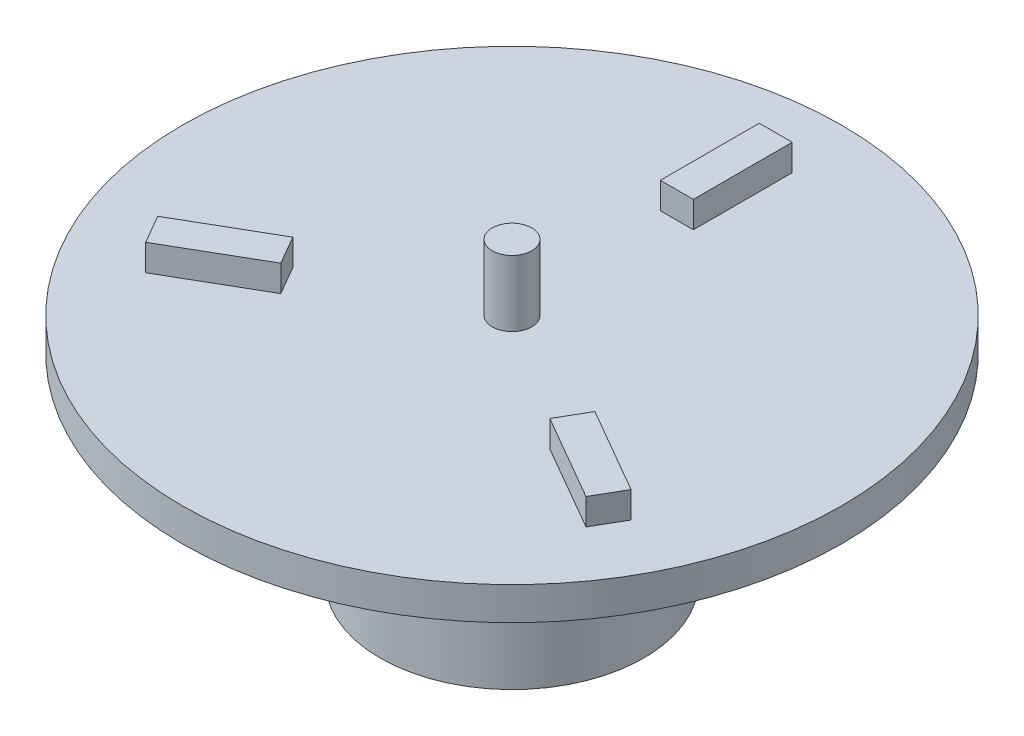
SolidWorks part; units mm, degrees
ref_plane "Plan de face" through (0, 0, 0) normal (0, 0, 1) x (1, 0, 0)
ref_plane "Plan de dessus" through (0, 0, 0) normal (0, 1, 0) x (1, 0, 0)
ref_plane "Plan de droite" through (0, 0, 0) normal (1, 0, 0) x (0, 0, -1)
sketch "Esquisse1" plane through (0, 0, 0) normal (0, 1, 0) x (1, 0, 0)
  circle A0 centre (0, 0) radius 4
  dimension "D1" = 8
extrude "Boss.-Extru.1" add sketch "Esquisse1" along normal blind 5
sketch "Esquisse4" plane through (0, 5, 0) normal (0, 1, 0) x (1, 0, 0)
  circle A0 centre (0, 0) radius 5.5
  dimension "D1" = 11
extrude "Boss.-Extru.3" add sketch "Esquisse4" along normal blind 1
sketch "Esquisse5" plane through (0, 6, 0) normal (0, 1, 0) x (1, 0, 0)
  circle A0 centre (0, 0) radius 10
  dimension "D1" = 20
extrude "Boss.-Extru.4" add sketch "Esquisse5" along normal blind 1
sketch "Esquisse6" plane through (0, 7, 0) normal (0, 1, 0) x (1, 0, 0)
  circle A0 centre (0, 0) radius 0.6
  dimension "D1" = 1.2
extrude "Boss.-Extru.5" add sketch "Esquisse6" along normal blind 2
sketch "Esquisse7" plane through (0, 7, 0) normal (0, 1, 0) x (1, 0, 0)
  line L0 (0, 0) -> (0, 5) construction
  line L1 (0, 5) -> (0.5, 5)
  line L2 (0.5, 5) -> (0.5, 8)
  line L3 (0.5, 8) -> (-0.5, 8)
  line L4 (-0.5, 8) -> (-0.5, 5)
  line L5 (-0.5, 5) -> (0, 5)
  dimension "D1" = 5
  dimension "D2" = 0.5
  dimension "D3" = 0.5
  dimension "D4" = 3
extrude "Boss.-Extru.6" add sketch "Esquisse7" along normal blind 0.8
pattern_circular "Répétition circulaire1" count 3 every 120 about axis through (0, 7, 0) along (0, 1, 0) of "Boss.-Extru.6"
